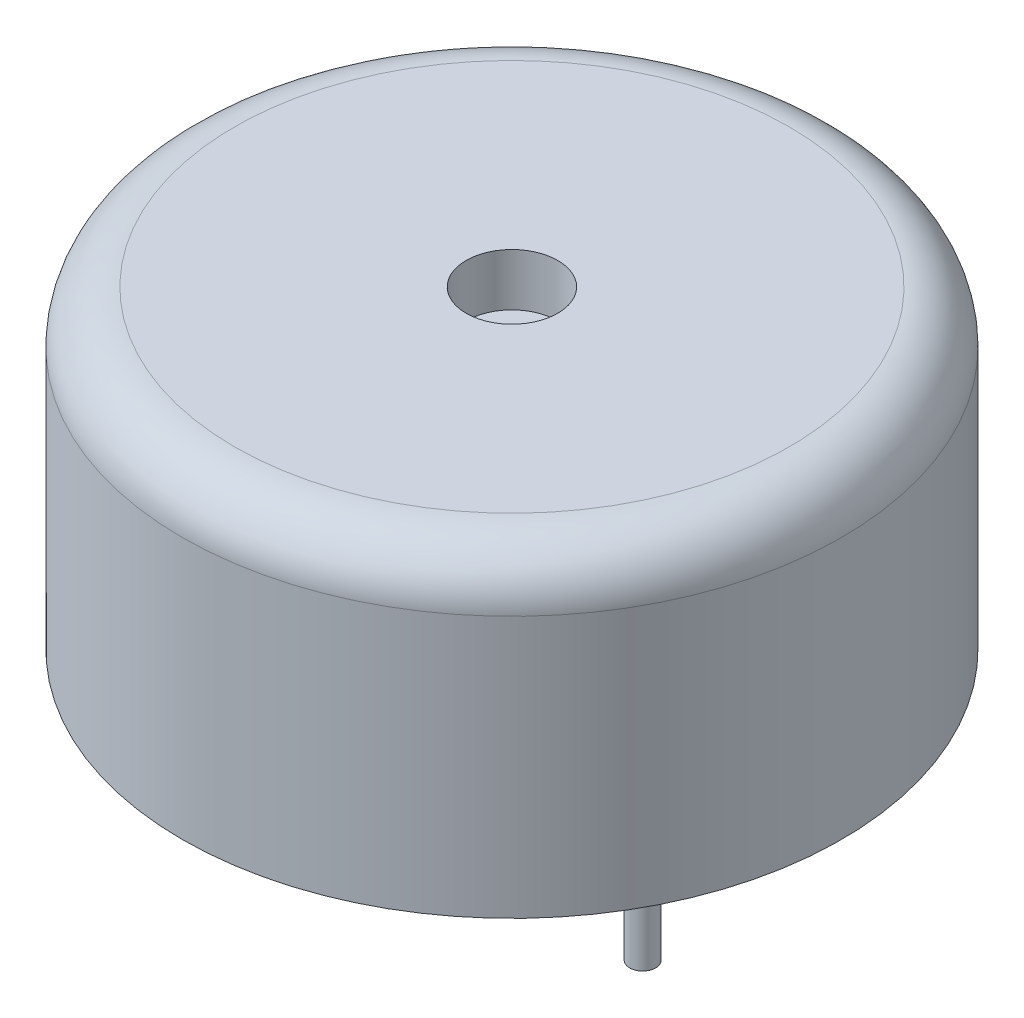
SolidWorks part; units mm, degrees
ref_plane "Front" through (0, 0, 0) normal (0, 0, 1) x (1, 0, 0)
ref_plane "Top" through (0, 0, 0) normal (0, 1, 0) x (1, 0, 0)
ref_plane "Right" through (0, 0, 0) normal (1, 0, 0) x (0, 0, -1)
sketch "Эскиз1" plane through (0, 0, 0) normal (0, 1, 0) x (1, 0, 0)
  line L0 (-8.1002, 0) -> (9.0203, 0) construction
  line L1 (0, 7.7779) -> (0, -9.0548) construction
  circle A0 centre (0, 0) radius 6.3
  circle A1 centre (2.5, 0) radius 1.25
  circle A3 centre (2.5, 0) radius 0.25
  circle A4 centre (-2.5, 0) radius 0.25
  circle A5 centre (-2.5, 0) radius 1.25
  circle A6 centre (0, 3.75) radius 0.5
  circle A7 centre (0, -3.75) radius 0.5
  circle A8 centre (0, 0) radius 0.8752
  dimension "D1" = 12.6
  dimension "D3" = 2.5
  dimension "D4" = 0.5
  dimension "D6" = 1
  dimension "D7" = 1.7505
  dimension "D2" = 2.5
  dimension "D5" = 3.75
extrude "Бобышка-Вытянуть1" add sketch "Эскиз1" along normal blind 6 contours A0 A5 A1 A6 A7 | A5 A4 | A4 | A1 A3 | A3 | A6 | A7 | A8 region at (-6.1218, 0, 0) region at (1.2854, 0, 0) region at (2.5, 0, 0) region at (-2.5, 0, 0) region at (-3.7146, 0, 0) region at (0, 0, -3.75) region at (0, 0, 3.75) region at (0, 0, 0)
fillet "Скругление1" radius 1 1 edges at (0, 6, 6.3)
extrude "Вырез-Вытянуть1" cut sketch "Эскиз1<3>" against normal blind 1 from surface contours A8 region at (0, 0, 0) starting at face at (0, 6, 5.3)
sketch "Эскиз1<3>" plane through (0, 0, 0) normal (0, 1, 0) x (1, 0, 0) same geometry as "Эскиз1"
extrude "Бобышка-Вытянуть2" add sketch "Эскиз1<4>" against normal blind 0.9 contours A5 A4 | A7 | A1 A3 | A3 | A4 | A6 region at (1.2854, 0, 0) region at (2.5, 0, 0) region at (-2.5, 0, 0) region at (-3.7146, 0, 0) region at (0, 0, -3.75) region at (0, 0, 3.75)
sketch "Эскиз1<4>" plane through (0, 0, 0) normal (0, 1, 0) x (1, 0, 0) same geometry as "Эскиз1"
fillet "Скругление2" radius 0.2 2 edges at (2.5, -0.9, 1.25) (-2.5, -0.9, 1.25)
extrude "Бобышка-Вытянуть3" add sketch "Эскиз1<5>" against normal blind 3 from surface contours A4 | A3 region at (2.5, 0, 0) region at (-2.5, 0, 0) starting at face at (-2.5, -0.9, 1.05)
sketch "Эскиз1<5>" plane through (0, 0, 0) normal (0, 1, 0) x (1, 0, 0) same geometry as "Эскиз1"
